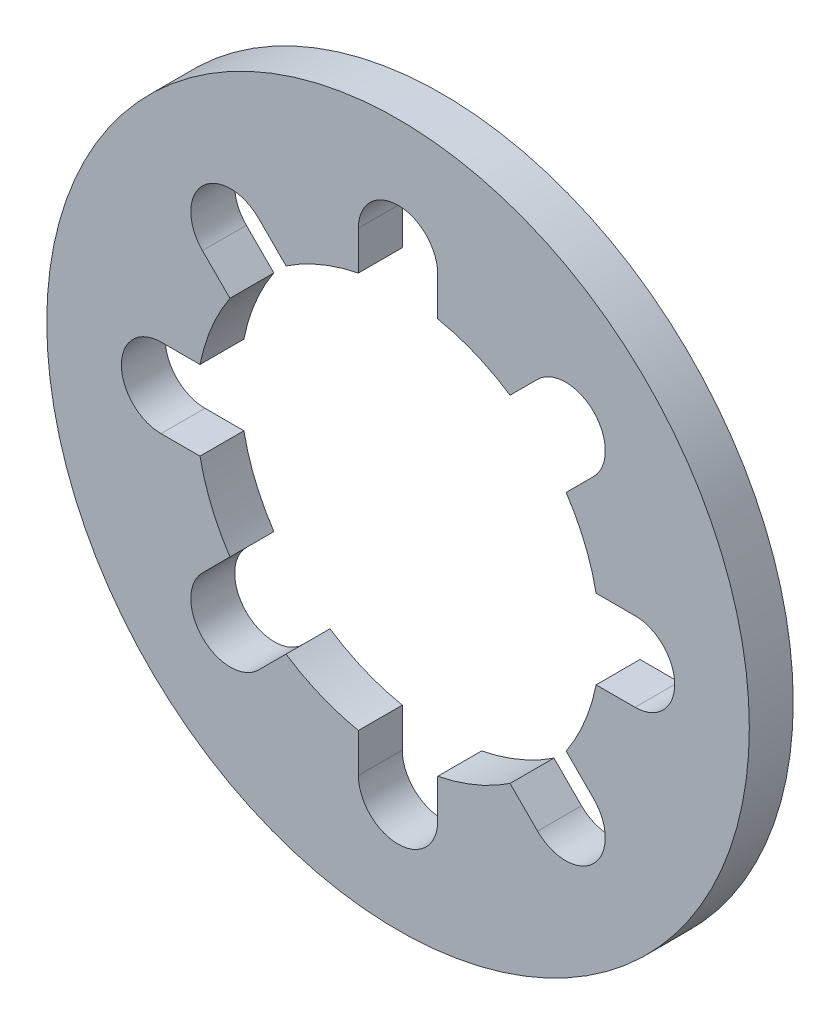
SolidWorks part; units mm, degrees
ref_plane "Front" through (0, 0, 0) normal (0, 0, 1) x (1, 0, 0)
ref_plane "Top" through (0, 0, 0) normal (0, 1, 0) x (1, 0, 0)
ref_plane "Right" through (0, 0, 0) normal (1, 0, 0) x (0, 0, -1)
sketch "Sketch1" plane through (0, 0, 0) normal (0, 0, 1) x (1, 0, 0)
  circle A0 centre (0, 0) radius 4
  circle A1 centre (0, 0) radius 2.3
extrude "Base-Extrude" add sketch "Sketch1" against normal blind 0.5
sketch "Sketch2" plane through (-2.5554, 2.7609, 0) normal (0, 0, 1) x (1, 0, 0)
  line L0 (2.5554, -2.7609) -> (10.5554, -2.7609) construction
  line L1 (2.5554, -2.7609) -> (2.5554, -0.9214) construction
  line L2 (2.1038, -0.5057) -> (2.1038, -0.0625)
  line L3 (3.007, -0.0625) -> (3.007, -0.5057)
  line L4 (3.007, -0.5057) -> (2.1038, -0.5057)
  circle A0 centre (2.5554, -2.7609) radius 3.15 construction
  arc A1 (2.1038, -0.0625) -> (3.007, -0.0625) centre (2.5554, -0.0625) cw
  circle A5 centre (2.5554, -2.7609) radius 2.3 construction
  dimension "D2" = 6.3
  dimension "D1" = 8
  dimension "D3" = 0.9032
extrude "TypeBSlot" cut sketch "Sketch2" against normal through all
pattern_circular "TypeBPattern" count 8 over 360 about axis through (0, 0, -0.5) along (0, 0, 1) of "TypeBSlot"
equation "\"D2@Sketch2\" =  ( \"D0@Sketch1\" + \"d@Sketch1\" )  / 2"
equation "\"D3@Sketch2\" = \"d@Sketch1\" * 3.14159 / \"D1@Sketch2\" / 2"
